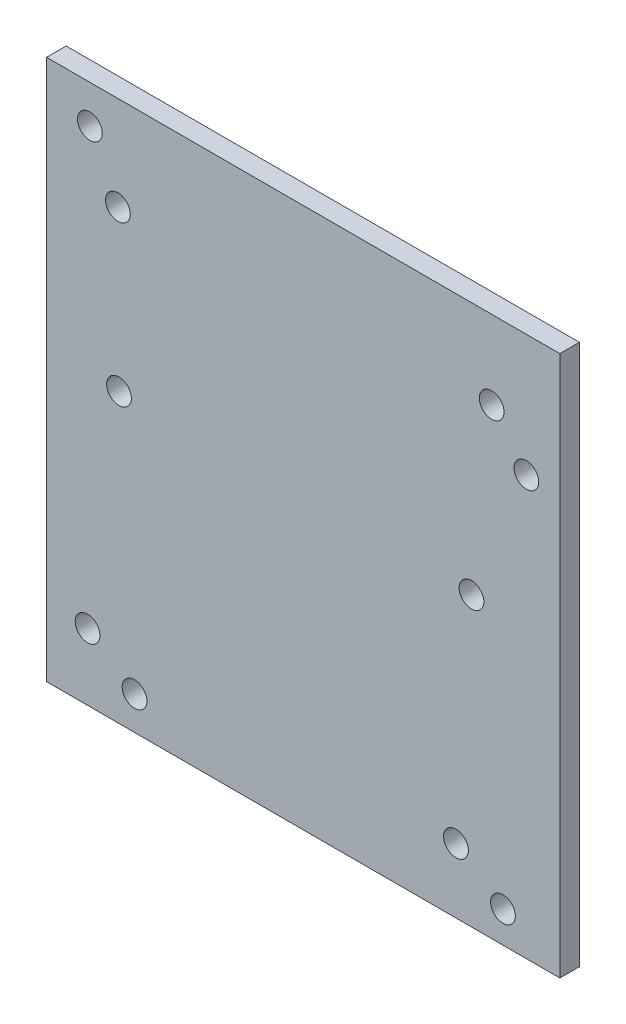
SolidWorks part; units mm, degrees
ref_plane "Front Plane" through (0, 0, 0) normal (0, 0, 1) x (1, 0, 0)
ref_plane "Top Plane" through (0, 0, 0) normal (0, 1, 0) x (1, 0, 0)
ref_plane "Right Plane" through (0, 0, 0) normal (1, 0, 0) x (0, 0, -1)
sketch "Sketch1" plane through (0, 0, 0) normal (0, 0, 1) x (1, 0, 0)
  line L0 (-570.3819, 236.4783) -> (-570.3819, 211.0783) construction
  line L5 (-570.3819, 211.0783) -> (-540.0489, 211.0783) construction
  line L6 (-540.0489, 211.0783) -> (-540.0489, 236.4783) construction
  line L7 (-540.0489, 236.4783) -> (-570.3819, 236.4783) construction
  line L8 (-532.8862, 362.9134) -> (-560.1463, 365.8966) construction
  line L9 (-560.1463, 365.8966) -> (-560.5461, 336.3644) construction
  line L10 (-560.5461, 336.3644) -> (-533.286, 333.3813) construction
  line L11 (-533.286, 333.3813) -> (-532.8862, 362.9134) construction
  line L12 (-659.3105, 377.0773) -> (-686.7338, 380.0783) construction
  line L13 (-686.7338, 380.0783) -> (-692.9825, 350.529) construction
  line L14 (-692.9825, 350.529) -> (-665.5591, 347.5279) construction
  line L15 (-665.5591, 347.5279) -> (-659.3105, 377.0773) construction
  line L16 (-660.6408, 211.0783) -> (-660.6408, 236.4783) construction
  line L17 (-660.6408, 236.4783) -> (-690.9738, 236.4783) construction
  line L18 (-690.9738, 236.4783) -> (-690.9738, 211.0783) construction
  line L19 (-690.9738, 211.0783) -> (-660.6408, 211.0783) construction
  line L20 (-570.3819, 236.4783) -> (-570.3819, 211.0783) construction
  line L21 (-570.3819, 211.0783) -> (-540.0489, 211.0783) construction
  line L22 (-540.0489, 211.0783) -> (-540.0489, 236.4783) construction
  line L23 (-540.0489, 236.4783) -> (-570.3819, 236.4783) construction
  line L24 (-532.8862, 362.9134) -> (-560.1463, 365.8966) construction
  line L25 (-560.1463, 365.8966) -> (-560.5461, 336.3644) construction
  line L26 (-560.5461, 336.3644) -> (-533.286, 333.3813) construction
  line L27 (-533.286, 333.3813) -> (-532.8862, 362.9134) construction
  line L28 (-659.3105, 377.0773) -> (-686.7338, 380.0783) construction
  line L29 (-686.7338, 380.0783) -> (-692.9825, 350.529) construction
  line L30 (-692.9825, 350.529) -> (-665.5591, 347.5279) construction
  line L31 (-665.5591, 347.5279) -> (-659.3105, 377.0773) construction
  line L32 (-660.6408, 211.0783) -> (-660.6408, 236.4783) construction
  line L33 (-660.6408, 236.4783) -> (-690.9738, 236.4783) construction
  line L34 (-690.9738, 236.4783) -> (-690.9738, 211.0783) construction
  line L35 (-690.9738, 211.0783) -> (-660.6408, 211.0783) construction
  line L36 (-686.7338, 380.0783) -> (-540.0489, 211.0783) construction
  line L37 (-690.9738, 211.0783) -> (-532.8862, 362.9134) construction
  line L39 (-696.1575, 207.9033) -> (-529.7112, 207.9033)
  line L40 (-696.1575, 207.9033) -> (-696.1575, 383.2533)
  line L41 (-696.1575, 383.2533) -> (-529.7112, 383.2533)
  line L42 (-529.7112, 207.9033) -> (-529.7112, 383.2533)
  line L43 (-696.1575, 207.9033) -> (-529.7112, 383.2533) construction
  line L44 (-696.1575, 383.2533) -> (-529.7112, 207.9033) construction
  circle A0 centre (-548.1569, 218.0633) radius 2.5273 construction
  circle A1 centre (-563.3969, 228.8583) radius 2.5273 construction
  circle A2 centre (-540.573, 343.7606) radius 2.5273 construction
  circle A3 centre (-551.816, 357.7668) radius 2.5273 construction
  circle A4 centre (-673.0254, 352.7515) radius 2.5273 construction
  circle A5 centre (-682.1218, 370.9328) radius 2.5273 construction
  circle A6 centre (-682.8658, 229.4933) radius 2.5273 construction
  circle A7 centre (-667.6258, 218.6983) radius 2.5273 construction
  circle A8 centre (-548.1569, 218.0633) radius 2.5273 construction
  circle A9 centre (-563.3969, 228.8583) radius 2.5273 construction
  circle A10 centre (-540.573, 343.7606) radius 2.5273 construction
  circle A11 centre (-551.816, 357.7668) radius 2.5273 construction
  circle A12 centre (-673.0254, 352.7515) radius 2.5273 construction
  circle A13 centre (-682.1218, 370.9328) radius 2.5273 construction
  circle A14 centre (-682.8658, 229.4933) radius 2.5273 construction
  circle A15 centre (-667.6258, 218.6983) radius 2.5273 construction
  circle A23 centre (-667.6258, 218.6983) radius 4.0127
  circle A24 centre (-682.8658, 229.4933) radius 4.0127
  circle A25 centre (-682.1218, 370.9328) radius 4.0127
  circle A26 centre (-673.0254, 352.7515) radius 4.0127
  circle A27 centre (-551.816, 357.7668) radius 4.0127
  circle A28 centre (-540.573, 343.7606) radius 4.0127
  circle A29 centre (-548.1569, 218.0633) radius 4.0127
  circle A30 centre (-563.3969, 228.8583) radius 4.0127
  circle A31 centre (-558.3616, 301.2062) radius 3 construction
  circle A32 centre (-672.6612, 301.2062) radius 3 construction
  circle A33 centre (-558.3616, 301.2062) radius 3 construction
  circle A34 centre (-672.6612, 301.2062) radius 3 construction
  circle A35 centre (-558.3616, 301.2062) radius 4.0132
  circle A36 centre (-672.6612, 301.2062) radius 4.0132
  point P1 (-608.6645, 290.1323)
  point P18 (-612.9344, 295.5783)
  dimension "D5" = 8.0254
  dimension "D6" = 8.0264
  dimension "D1" = 3.175
  dimension "D2" = 3.175
  dimension "D3" = 3.175
  dimension "D4" = 3.175
extrude "Boss-Extrude1" add sketch "Sketch1" along normal blind 6.35
